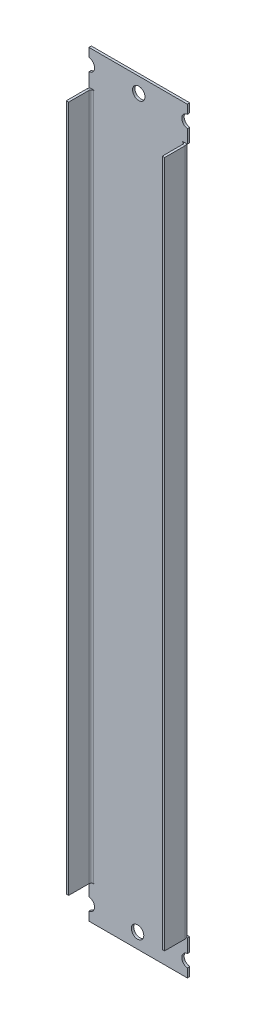
SolidWorks part; units mm, degrees
note: The reader was unsure of these and kept them because the rebuilt part matched: flange length of "Brida de arista1".
ref_plane "Alzado" through (0, 0, 0) normal (0, 0, 1) x (1, 0, 0)
ref_plane "Planta" through (0, 0, 0) normal (0, 1, 0) x (1, 0, 0)
ref_plane "Vista lateral" through (0, 0, 0) normal (1, 0, 0) x (0, 0, -1)
sketch "Croquis1" plane through (0, 0, 0) normal (0, 0, 1) x (1, 0, 0)
  line L0 (0, 231.775) -> (0, -231.775) construction
  line L1 (-31.369, -241.3) -> (31.369, -241.3)
  line L2 (-31.369, -241.3) -> (-31.369, 241.3)
  line L3 (-31.369, 241.3) -> (31.369, 241.3)
  line L4 (31.369, -241.3) -> (31.369, 241.3)
  line L5 (-31.369, -241.3) -> (31.369, 241.3) construction
  line L6 (-31.369, 241.3) -> (31.369, -241.3) construction
  circle A0 centre (0.381, 231.775) radius 3.9624
  circle A1 centre (-0.381, -231.775) radius 3.9624
  point P0 (0, 0)
  point P12 (0, 0)
  dimension "D6" = 7.9248
  dimension "D1" = 482.6
  dimension "D2" = 62.738
  dimension "D3" = 463.55
  dimension "D5" = 30.988
  dimension "D4" = 30.988
base flange "Brida base1" sketch "Croquis1" thickness 1.524 reverse thickness direction no parameters "D1"=1.524
edge flange "Brida de arista1" sketch "Croquis12" flange profiles "Croquis12", "Croquis14" flange angle 90 flange length 16.002 flange position material inside bend radius 1.524 thickness 1.524 relief rectangular parameters "D6"=10, "D8"=1
sketch "Croquis12" plane through (31.369, 0, 0) normal (1, 0, 0) x (0, 1, 0)
  line L2 (-219.075, 0) -> (-219.075, 14.478)
  line L3 (-219.075, 14.478) -> (219.075, 14.478)
  line L4 (219.075, 14.478) -> (219.075, 0)
  line L7 (-241.3, 0) -> (241.3, 0) construction
  line L8 (-219.075, 0) -> (219.075, 0)
  line L9 (-241.3, 0) -> (-219.075, 0) construction
  line L10 (219.075, 0) -> (241.3, 0) construction
  dimension "D1" = 438.15
sketch "Croquis14" plane through (-31.369, 0, 0) normal (-1, 0, 0) x (0, -1, 0)
  line L0 (-241.3, 0) -> (241.3, 0) construction
  line L1 (-219.075, 0) -> (219.075, 0)
  line L2 (-219.075, 0) -> (-219.075, 14.478)
  line L3 (-219.075, 14.478) -> (219.075, 14.478)
  line L4 (219.075, 14.478) -> (219.075, 0)
bend "Pliegue de arista1" bend radius 1.524 bend angle 90 parameters "D5"=1
bend "Pliegue de arista2" bend radius 1.524 bend angle 90 parameters "D5"=3
sketch "Croquis15" plane through (0, 0, 0) normal (0, 0, 1) x (1, 0, 0)
  line L0 (0, 241.3) -> (0, -241.3) construction
  line L6 (31.369, 241.3) -> (-31.369, 241.3) construction
  line L23 (-31.369, -241.3) -> (31.369, -241.3) construction
  line L24 (-31.369, 241.3) -> (-31.369, 219.2274) construction
  circle A4 centre (-31.7754, 231.775) radius 3.9624
  circle A5 centre (-31.7754, -231.775) radius 3.9624
  circle A6 centre (31.7754, -231.775) radius 3.9624
  circle A7 centre (31.7754, 231.775) radius 3.9624
  dimension "D3" = 9.525
  dimension "D4" = 7.9248
  dimension "D1" = 0.4064
  dimension "D2" = 9.525
extrude "Cortar-Extruir1" cut sketch "Croquis15" against normal through all
sketch "Líneas de pliegue1" [suppressed] plane through (0, 0, 0) normal (0, 1, 0) x (1, 0, 0)
sketch "Cuadro delimitador1" [suppressed] plane through (0, 0, 0) normal (0, 1, 0) x (1, 0, 0)
sheet metal parameters "Chapa metálica1" thickness 1.524 parameters "D1"=6.35
flat pattern "Chapa desplegada1" [suppressed]
sketch "Líneas de pliegue2" plane through (0, 0, 0) normal (0, 1, 0) x (1, 0, 0)
sketch3d "Cuadro delimitador2" [suppressed]
  line L0 (-47.244, 241.3, 0) -> (-47.244, -241.3, 0) construction
  line L1 (47.244, 241.3, 0) -> (47.244, -241.3, 0) construction
  line L2 (-47.244, 241.3, 0) -> (47.244, 241.3, 0) construction
  line L3 (-47.244, -241.3, 0) -> (47.244, -241.3, 0) construction
sheet metal parameters "Chapa metálica2" thickness 1.524 parameters "D1"=6.35
flat pattern "Chapa desplegada1"
sketch "Líneas de pliegue2" plane through (0, 0, 0) normal (0, 0, 1) x (1, 0, 0)
  line L0 (204.7175, -219.075) -> (204.7175, 219.075) construction
  line L1 (204.7175, -219.075) -> (204.7175, 219.075) construction
  line L2 (-204.7175, 219.075) -> (-204.7175, -219.075) construction
  line L3 (-204.7175, 219.075) -> (-204.7175, -219.075) construction
sketch3d "Cuadro delimitador2" [suppressed]
  line L0 (219.443, 241.3, 0) -> (219.443, -241.3, 0) construction
  line L1 (-219.443, 241.3, 0) -> (-219.443, -241.3, 0) construction
  line L2 (219.443, 241.3, 0) -> (-219.443, 241.3, 0) construction
  line L3 (219.443, -241.3, 0) -> (-219.443, -241.3, 0) construction
bend of the flat pattern "Aplanar-<Pliegue de arista1>1"
bend of the flat pattern "Aplanar-<Pliegue de arista2>1"
sheet metal parameters "Chapa metálica3" thickness 1.524 parameters "D1"=6.35
flat pattern "Chapa desplegada1"
sketch "Líneas de pliegue2" plane through (0, 0, 0) normal (0, 0, 1) x (1, 0, 0)
  line L0 (204.7414, -219.075) -> (204.7414, 219.075) construction
  line L1 (204.7414, -219.075) -> (204.7414, 219.075) construction
  line L2 (-204.7414, 219.075) -> (-204.7414, -219.075) construction
  line L3 (-204.7414, 219.075) -> (-204.7414, -219.075) construction
sketch3d "Cuadro delimitador2" [suppressed]
  line L0 (219.4908, 241.3, 0) -> (219.4908, -241.3, 0) construction
  line L1 (-219.4908, 241.3, 0) -> (-219.4908, -241.3, 0) construction
  line L2 (219.4908, 241.3, 0) -> (-219.4908, 241.3, 0) construction
  line L3 (219.4908, -241.3, 0) -> (-219.4908, -241.3, 0) construction
bend of the flat pattern "Aplanar-<Pliegue de arista1>1"
bend of the flat pattern "Aplanar-<Pliegue de arista2>1"
sheet metal parameters "Chapa metálica5" thickness 1.524 parameters "D1"=6.35
flat pattern "Chapa desplegada1"
sketch "Líneas de pliegue2" plane through (0, 0, 0) normal (0, 0, 1) x (1, 0, 0)
  line L0 (-30.0925, 219.075) -> (-30.0925, -219.075) construction
  line L1 (30.0925, -219.075) -> (30.0925, 219.075) construction
  line L2 (-30.0925, 219.075) -> (-30.0925, -219.075) construction
  line L3 (30.0925, -219.075) -> (30.0925, 219.075) construction
sketch3d "Cuadro delimitador2" [suppressed]
  line L0 (44.818, 241.3, 0) -> (44.818, -241.3, 0) construction
  line L1 (-44.818, 241.3, 0) -> (-44.818, -241.3, 0) construction
  line L2 (44.818, 241.3, 0) -> (-44.818, 241.3, 0) construction
  line L3 (44.818, -241.3, 0) -> (-44.818, -241.3, 0) construction
bend of the flat pattern "Aplanar-<Pliegue de arista2>3"
bend of the flat pattern "Aplanar-<Pliegue de arista1>3"
sheet metal parameters "Chapa metálica6" thickness 1.524 parameters "D1"=6.35
flat pattern "Chapa desplegada6"
sketch "Líneas de pliegue4" plane through (-205.994, 0, 0) normal (-1, 0, 0) x (0, 0, 1)
  line L0 (-0.2475, 219.075) -> (-0.2475, -219.075) construction
  line L1 (-0.2475, 219.075) -> (-0.2475, -219.075) construction
sketch3d "Cuadro delimitador4" [suppressed]
  line L0 (-2.019, 219.075, 0) -> (-2.019, -219.075, 0) construction
  line L1 (14.478, 219.075, 0) -> (14.478, -219.075, 0) construction
  line L2 (-2.019, 219.075, 0) -> (14.478, 219.075, 0) construction
  line L3 (-2.019, -219.075, 0) -> (14.478, -219.075, 0) construction
bend of the flat pattern "Aplanar-<Pliegue de arista2>2"
sheet metal parameters "Chapa metálica7" thickness 1.524 parameters "D1"=6.35
flat pattern "Chapa desplegada7" [suppressed]
sketch "Líneas de pliegue5" plane through (0, 0, 0) normal (0, 1, 0) x (1, 0, 0)
sketch "Cuadro delimitador5" [suppressed] plane through (0, 0, 0) normal (0, 1, 0) x (1, 0, 0)
bend of the flat pattern "Aplanar-<Pliegue de arista1>2"
equation "\"A\"=2.47"
equation "\"B\"=1.22"
equation "\"D2@Croquis1\"= \"A\""
